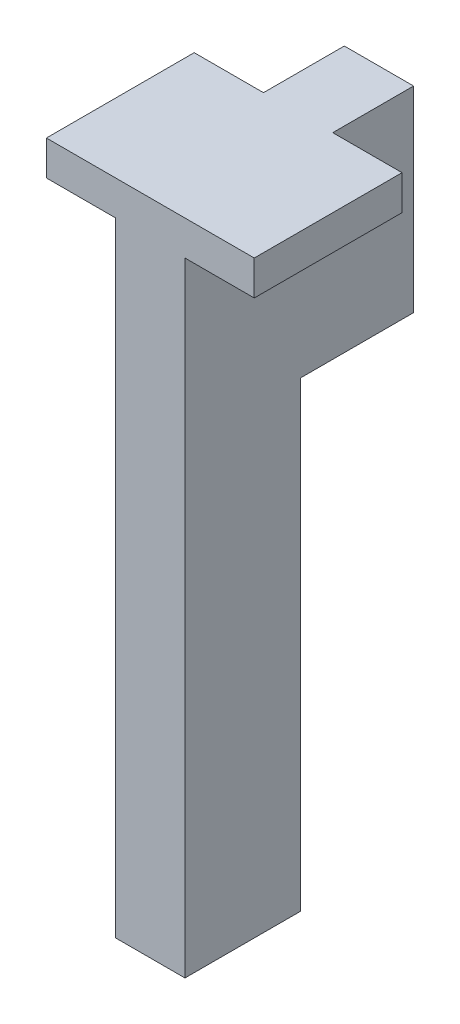
SolidWorks part; units mm, degrees
ref_plane "Front Plane" through (0, 0, 0) normal (0, 0, 1) x (1, 0, 0)
ref_plane "Top Plane" through (0, 0, 0) normal (0, 1, 0) x (1, 0, 0)
ref_plane "Right Plane" through (0, 0, 0) normal (1, 0, 0) x (0, 0, -1)
sketch "Sketch1" plane through (0, 0, 0) normal (0, 0, 1) x (1, 0, 0)
  line L0 (-1.5, -8.5) -> (1.5, -8.5)
  line L1 (1.5, -8.5) -> (1.5, -1.5)
  line L2 (1.5, -1.5) -> (4.5, -1.5)
  line L3 (4.5, -1.5) -> (4.5, 0)
  line L4 (4.5, 0) -> (-4.5, 0)
  line L5 (-4.5, 0) -> (-4.5, -1.5)
  line L6 (-4.5, -1.5) -> (-1.5, -1.5)
  line L7 (-1.5, -1.5) -> (-1.5, -8.5)
  point P6 (0, -8.5)
  dimension "D1" = 3
  dimension "D2" = 7
  dimension "D3" = 3
  dimension "D4" = 1.5
extrude "Boss-Extrude1" add sketch "Sketch1" along normal blind 9.9
sketch "Sketch2" plane through (1.5, 0, 0) normal (1, 0, 0) x (0, 0, -1)
  line L0 (-9.9, -8.5) -> (-4.9, -8.5)
  line L1 (-9.9, -8.5) -> (-9.9, -28.5)
  line L2 (-4.9, -8.5) -> (-4.9, -28.5)
  line L3 (-9.9, -28.5) -> (-4.9, -28.5)
  line L4 (-9.9, -8.5) -> (0, -8.5) construction
  dimension "D1" = 5
  dimension "D2" = 20
extrude "Boss-Extrude2" add sketch "Sketch2" against normal up to surface (3 mm away) up to face at (-1.5, -5, 4.95)
sketch "Sketch3" plane through (0, 0, 0) normal (0, 1, 0) x (1, 0, 0)
  line L0 (4.5, 0) -> (1.5, 0)
  line L1 (4.5, 0) -> (4.5, -3.5)
  line L2 (1.5, 0) -> (1.5, -3.5)
  line L3 (4.5, -3.5) -> (1.5, -3.5)
  line L4 (1.5, 0) -> (4.5, 0) construction
  point P0 (0, 0)
  point P7 (0, 0)
  point P13 (0, 0)
  point P14 (0, 0)
  point P15 (1.0038, 0)
  dimension "D1" = 3.5
extrude "Cut-Extrude1" cut sketch "Sketch3" against normal up to surface (1.5 mm away) up to face at (3, -1.5, 4.95)
mirror "Mirror1" about plane through (0, 0, 0) normal (1, 0, 0) of "Cut-Extrude1"
